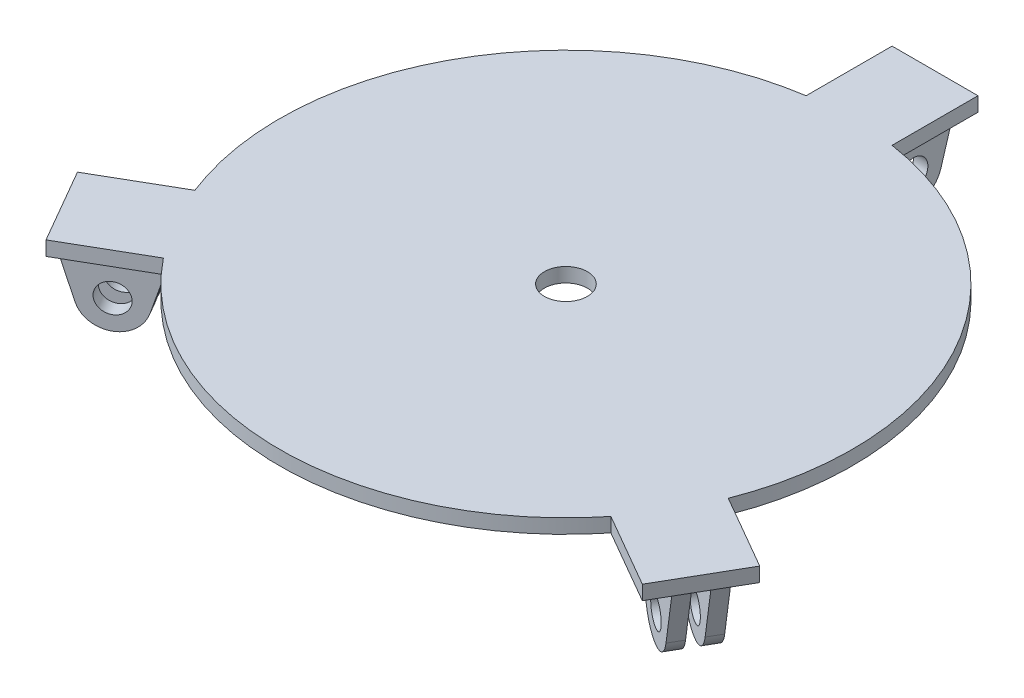
SolidWorks part; units mm, degrees
material "1023 Carbon Steel Sheet (SS)"
ref_plane "Front Plane" through (0, 0, 0) normal (0, 0, 1) x (1, 0, 0)
ref_plane "Top Plane" through (0, 0, 0) normal (0, 1, 0) x (1, 0, 0)
ref_plane "Right Plane" through (0, 0, 0) normal (1, 0, 0) x (0, 0, -1)
sketch "Sketch1" plane through (0, 0, 0) normal (0, 1, 0) x (1, 0, 0)
  line L0 (-15, 98.8686) -> (-15, 128.8686)
  line L1 (-15, 128.8686) -> (15, 128.8686)
  line L2 (15, 128.8686) -> (15, 98.8686)
  line L3 (93.1227, -36.4439) -> (119.1035, -51.4439)
  line L4 (119.1035, -51.4439) -> (104.1035, -77.4247)
  line L5 (104.1035, -77.4247) -> (78.1227, -62.4247)
  line L6 (-78.1227, -62.4247) -> (-104.1035, -77.4247)
  line L7 (-104.1035, -77.4247) -> (-119.1035, -51.4439)
  line L8 (-119.1035, -51.4439) -> (-93.1227, -36.4439)
  line L9 (0, 100) -> (0, -100) construction
  line L10 (0, 0) -> (-111.6035, -64.4343) construction
  line L11 (0, 0) -> (111.6035, -64.4343) construction
  line L12 (0, 0) -> (0, 128.8686) construction
  circle A0 centre (0, 0) radius 7.5
  arc A1 (-78.1227, -62.4247) -> (78.1227, -62.4247) centre (0, 0) ccw
  arc A2 (93.1227, -36.4439) -> (15, 98.8686) centre (0, 0) ccw
  arc A3 (-15, 98.8686) -> (-93.1227, -36.4439) centre (0, 0) ccw
  point P18 (81.7471, -33.2143)
  point P21 (79.0545, -28.3216)
  dimension "D4" = 200
  dimension "D5" = 15
  dimension "D1" = 120
  dimension "D2" = 30
  dimension "D3" = 30
extrude "Boss-Extrude2" add sketch "Sketch1" along normal blind 5 contours L0 A3 L8 L7 L6 A1 L5 L4 L3 A2 L2 L1 A0 region at (-11.6966, 0, -113.8686)
sketch "Sketch4" plane through (0, 0, 0) normal (1, 0, 0) x (0, 0, -1)
  line L0 (104.2992, -17.9028) -> (98.8686, 0)
  line L1 (128.8686, 0) -> (98.8686, 0) construction
  line L2 (98.8686, 0) -> (128.8686, 0)
  line L3 (128.8686, 0) -> (123.438, -17.9028)
  line L4 (113.8686, -15) -> (113.8686, 0) construction
  circle A0 centre (113.8686, -15) radius 5
  arc A1 (104.2992, -17.9028) -> (123.438, -17.9028) centre (113.8686, -15) ccw
  point P4 (111.7322, -15.6581)
  point P11 (113.8686, -15.6581)
  point P14 (104.4772, -11.5647)
  dimension "D1" = 10
  dimension "D2" = 5
  dimension "D3" = 15
extrude "Boss-Extrude5" add sketch "Sketch4" along normal blind 5 from offset 2.5
extrude "Boss-Extrude6" add sketch "Sketch4<2>" against normal blind 5 from offset 2.5 offset against normal yes
sketch "Sketch4<2>" plane through (0, 0, 0) normal (1, 0, 0) x (0, 0, -1) same geometry as "Sketch4"
pattern_circular "CirPattern5" count 3 over 240 about axis through (0, 0, 0) along (0, 1, 0) of "Boss-Extrude5", "Boss-Extrude6"
